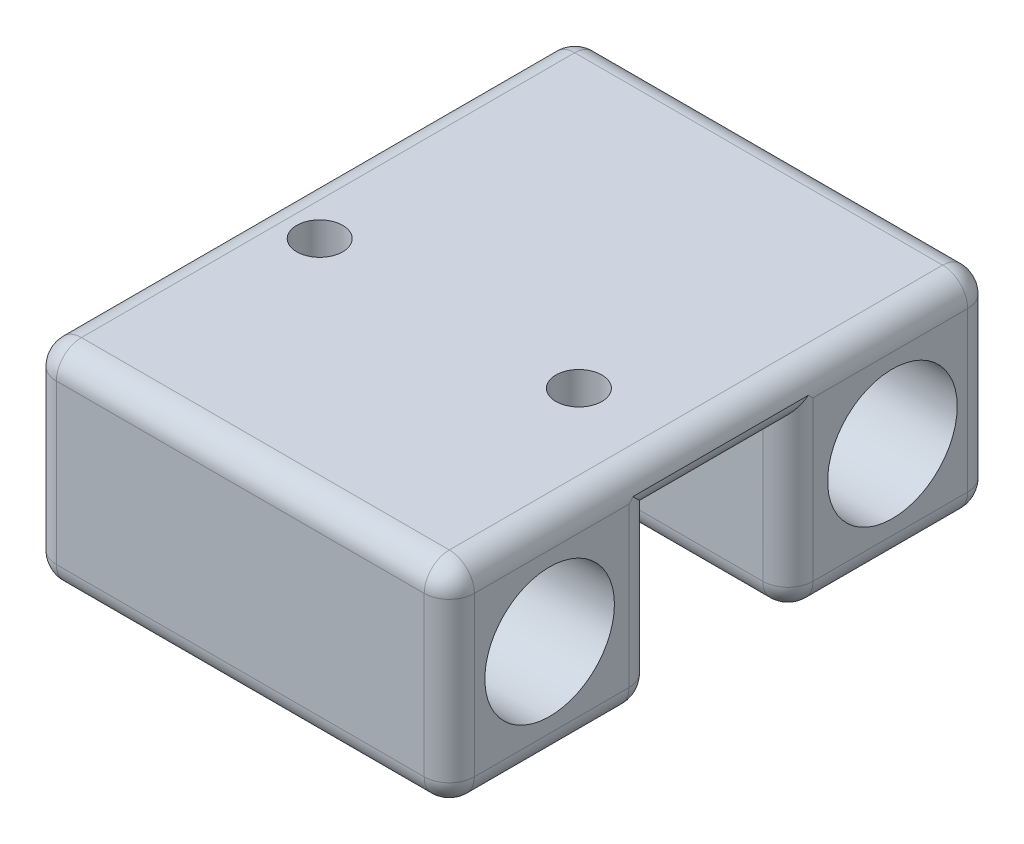
SolidWorks part; units mm, degrees
ref_plane "前视基准面" through (0, 0, 0) normal (0, 0, 1) x (1, 0, 0)
ref_plane "上视基准面" through (0, 0, 0) normal (0, 1, 0) x (1, 0, 0)
ref_plane "右视基准面" through (0, 0, 0) normal (1, 0, 0) x (0, 0, -1)
sketch "草图1" plane through (0, 0, 0) normal (0, 1, 0) x (1, 0, 0)
  line L1 (-17.6562, 11.7969) -> (32.3438, 11.7969)
  line L2 (-17.6562, 11.7969) -> (-17.6562, -53.2031)
  line L3 (-17.6562, -53.2031) -> (32.3438, -53.2031)
  line L4 (32.3438, 11.7969) -> (32.3438, -53.2031)
  line L5 (-17.6562, 11.7969) -> (32.3438, -53.2031) construction
  line L6 (-17.6562, -53.2031) -> (32.3438, 11.7969) construction
  point P4 (7.3438, -20.7031)
  dimension "D1" = 50
  dimension "D2" = 65
extrude "凸台-拉伸1" add sketch "草图1" along normal blind 25
sketch "草图2" plane through (32.3438, 0, 0) normal (1, 0, 0) x (0, 0, -1)
  line L0 (-53.2031, 12.5) -> (11.7969, 12.5) construction
  line L1 (-53.2031, 25) -> (-53.2031, 0) construction
  line L2 (11.7969, 25) -> (11.7969, 0) construction
  line L3 (-20.7031, 25) -> (-20.7031, 0) construction
  line L4 (-53.2031, 25) -> (11.7969, 25) construction
  line L5 (-53.2031, 0) -> (11.7969, 0) construction
  line L7 (-28.7031, 20) -> (-12.7031, 20)
  line L8 (-28.7031, 20) -> (-28.7031, -1.8926)
  line L9 (-28.7031, -1.8926) -> (-12.7031, -1.8926)
  line L10 (-12.7031, 20) -> (-12.7031, -1.8926)
  line L11 (-20.7031, -1.8926) -> (-20.7031, 20) construction
  line L12 (-28.7031, 9.0537) -> (-12.7031, 9.0537) construction
  circle A0 centre (-41.2031, 12.5) radius 7.75
  circle A1 centre (-0.2031, 12.5) radius 7.75
  point P16 (-20.7031, 9.0537)
  dimension "D1" = 15.5
  dimension "D2" = 15.5
  dimension "D3" = 12
  dimension "D4" = 12
  dimension "D5" = 16
  dimension "D6" = 5
extrude "切除-拉伸1" cut sketch "草图2" against normal through all
sketch "草图3" plane through (0, 25, 0) normal (0, 1, 0) x (1, 0, 0)
  circle A0 centre (-10.6563, -25.7031) radius 2.75
  circle A1 centre (20.3437, -25.7031) radius 2.75
sketch "草图4" plane through (0, 25, 0) normal (0, 1, 0) x (1, 0, 0)
  circle A0 centre (20.3437, -25.7031) radius 2.75
  circle A1 centre (-10.6563, -25.7031) radius 2.75
extrude "切除-拉伸3" cut sketch "草图4" against normal blind 5
fillet "圆角1" radius 3 22 edges at (32.3438, 0, 40.9531) (-17.6562, 0, 40.9531) (32.3438, 12.5, 53.2031) (7.3438, 25, 53.2031) (32.3438, 25, 20.7031) (7.3438, 25, -11.7969) (-17.6562, 25, 20.7031) (-17.6562, 12.5, 53.2031) (-17.6562, 12.5, -11.7969) (32.3438, 0, 0.4531) (32.3438, 12.5, -11.7969) (32.3438, 10, 12.7031) (32.3438, 20, 20.7031) (32.3438, 10, 28.7031) (-17.6563, 0, 0.4531) (-17.6563, 10, 12.7031) (-17.6563, 20, 20.7031) (-17.6563, 10, 28.7031) (7.3438, 0, -11.7969) (7.3437, 0, 12.7031) (7.3438, 0, 28.7031) (7.3438, 0, 53.2031)
